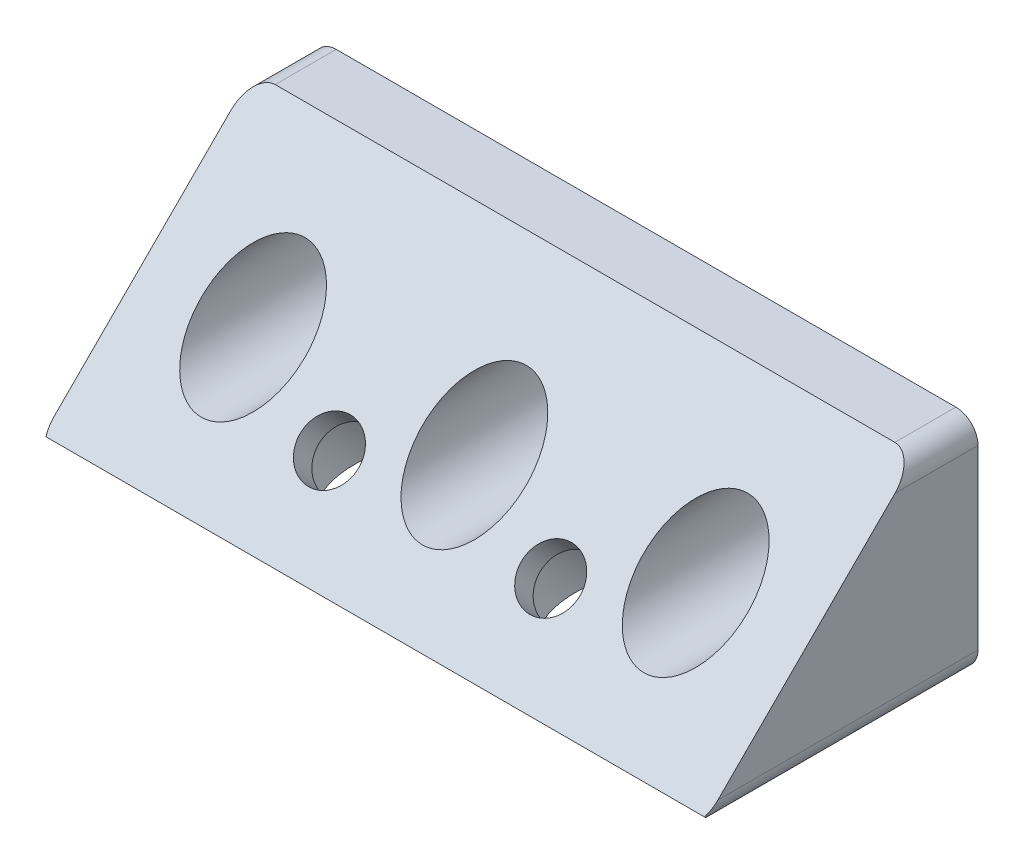
SolidWorks part; units mm, degrees
material "6061 Alloy"
ref_plane "Front Plane" through (0, 0, 0) normal (0, 0, 1) x (1, 0, 0)
ref_plane "Top Plane" through (0, 0, 0) normal (0, 1, 0) x (1, 0, 0)
ref_plane "Right Plane" through (0, 0, 0) normal (1, 0, 0) x (0, 0, -1)
sketch "Sketch3" plane through (0, 0, 0) normal (0, 0, 1) x (1, 0, 0)
  line L1 (0, 0) -> (76.2, 0)
  line L2 (0, 0) -> (0, 25.4)
  line L3 (0, 25.4) -> (76.2, 25.4)
  line L4 (76.2, 0) -> (76.2, 25.4)
  dimension "D1" = 25.4
  dimension "D2" = 76.2
extrude "Boss-Extrude1" add sketch "Sketch3" along normal blind 31.75
hole_wizard "CBORE for 1/4 Button Head Cap Screw1" positions "Sketch4" profile "Sketch5" counterbore size "1/4" standard "ANSI Inch" end condition up to next
sketch "Sketch4" plane through (0, 0, 31.75) normal (0, 0, 1) x (1, 0, 0)
  line L0 (76.2, 25.4) -> (0, 25.4) construction
  line L1 (0, 25.4) -> (0, 0) construction
  line L2 (76.2, 0) -> (76.2, 25.4) construction
  point P0 (12.7, 12.7)
  point P2 (38.1, 12.7)
  point P4 (63.5, 12.7)
  dimension "D1" = 12.7
  dimension "D2" = 12.7
  dimension "D3" = 12.7
  dimension "D4" = 12.7
  dimension "D5" = 25.4
  dimension "D6" = 25.4
  dimension "D7" = 12.7
sketch "Sketch5" plane through (12.7, 12.7, 31.75) normal (1, 0, 0) x (0, -1, 0)
  line L0 (0, 0) -> (0, 31.75)
  line L1 (0, 31.75) -> (3.3782, 31.75)
  line L3 (3.3782, 31.75) -> (3.3782, 28.7528)
  line L4 (3.3782, 28.7528) -> (5.9538, 28.7528)
  line L5 (5.9538, 28.7528) -> (5.9538, 0)
  line L7 (5.9538, 0) -> (0, 0)
  line L11 (0, -6.35) -> (0, 107.95) construction
  dimension "Thru Hole Dia." = 6.7564
  dimension "Thru Hole Depth" = 31.75
  dimension "C'Bore Dia." = 11.9075
  dimension "C'Bore Depth" = 28.7528
sketch "Sketch6" plane through (76.2, 0, 0) normal (1, 0, 0) x (0, 0, -1)
  line L0 (-7, 25.4) -> (-31.0807, 1.3193)
  line L1 (-31.75, 25.4) -> (0, 25.4) construction
  line L2 (-31.0807, 1.3193) -> (-29.7615, 0)
  line L3 (-31.75, 0) -> (0, 0) construction
  line L4 (0, 0) -> (0, 25.4) construction
  dimension "D1" = 7
  dimension "D2" = 45
extrude "Cut-Extrude1" cut sketch "Sketch6" against normal through all and the other way through all flip side to cut
ref_plane "Plane1" through (0, -1.7605, -1.7605) normal (0, 0.7071, 0.7071) x (1, 0, 0)
hole_wizard "CBORE for 1/4 Button Head Cap Screw2" positions "Sketch11" profile "Sketch12" counterbore size "1/4" standard "ANSI Inch" end condition up to next
sketch "Sketch11" plane through (0, -1.7605, -1.7605) normal (0, 0.7071, 0.7071) x (1, 0, 0)
  line L0 (0, -21.0445) -> (0, 13.0108) construction
  line L1 (76.2, 13.0108) -> (76.2, -21.0445) construction
  line L6 (0, -21.0445) -> (0, 0) construction
  point P0 (25.4, -10.5223)
  point P2 (50.8, -10.5223)
  point P5 (25.4, -10.5223)
  point P20 (25.4, -4.0169)
  point P21 (25.4, -4.3889)
  point P22 (25.4, -13.634)
  point P23 (25.4, -5.1421)
  point P28 (0, -10.5223)
  dimension "D1" = 25.4
  dimension "D2" = 25.4
  dimension "D3" = 25.4
  dimension "D4" = 0
  dimension "D5" = 0
sketch "Sketch12" plane through (25.4, -9.2009, 5.6799) normal (1, 0, 0) x (0, 0.7071, -0.7071)
  line L0 (0, 0) -> (0, 25.4)
  line L1 (0, 25.4) -> (3.3782, 25.4)
  line L3 (3.3782, 25.4) -> (3.3782, 22.4028)
  line L4 (3.3782, 22.4028) -> (5.9538, 22.4028)
  line L5 (5.9538, 22.4028) -> (5.9538, 0)
  line L7 (5.9538, 0) -> (0, 0)
  line L11 (0, -6.35) -> (0, 107.95) construction
  dimension "Thru Hole Dia." = 6.7564
  dimension "Thru Hole Depth" = 25.4
  dimension "C'Bore Dia." = 11.9075
  dimension "C'Bore Depth" = 22.4028
fillet "Fillet1" radius 2.54 4 edges at (0, 0, 14.8807) (0, 25.4, 3.5) (76.2, 25.4, 3.5) (76.2, 0, 14.8807)
